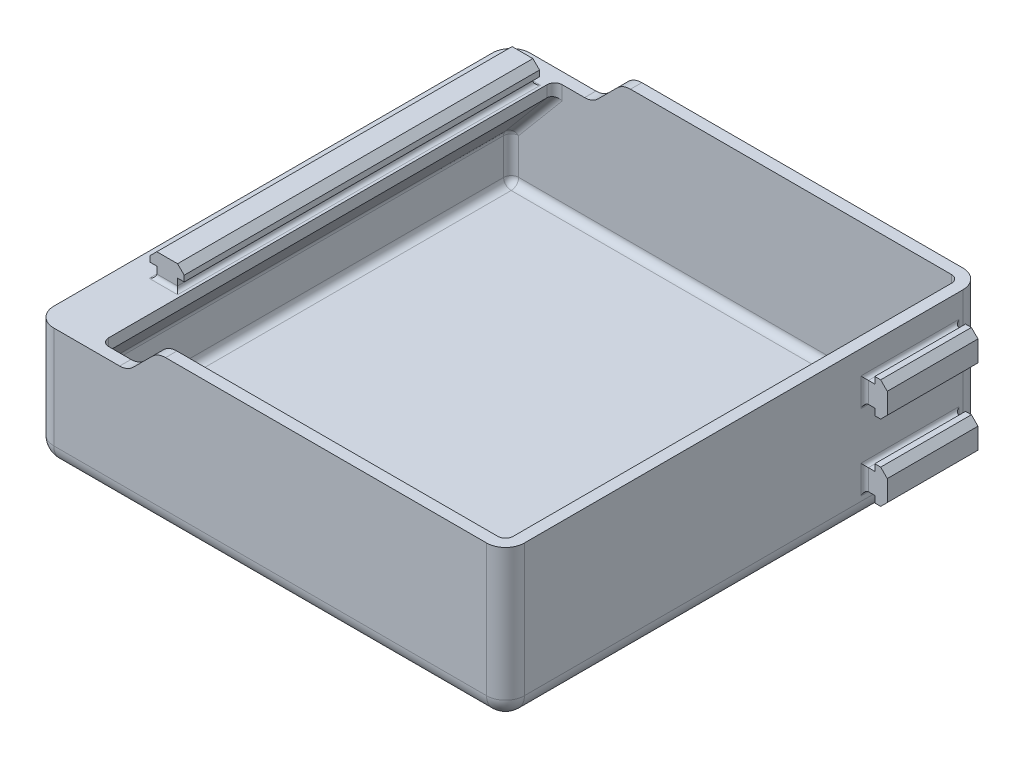
SolidWorks part; units mm, degrees
material "Hot Galvanized Steel"
ref_plane "Front" through (0, 0, 0) normal (0, 0, 1) x (1, 0, 0)
ref_plane "Top" through (0, 0, 0) normal (0, 1, 0) x (1, 0, 0)
ref_plane "Right" through (0, 0, 0) normal (1, 0, 0) x (0, 0, -1)
sketch "Sketch1" plane through (0, 0, 0) normal (0, 1, 0) x (1, 0, 0)
  line L1 (-62.25, -63) -> (62.25, -63)
  line L2 (-62.25, -63) -> (-62.25, 63)
  line L3 (-62.25, 63) -> (62.25, 63)
  line L4 (62.25, -63) -> (62.25, 63)
  line L5 (-62.25, -63) -> (62.25, 63) construction
  line L6 (-62.25, 63) -> (62.25, -63) construction
  point P0 (0, 0)
  dimension "D1" = 124.5
  dimension "D2" = 126
extrude "Boss-Extrude1" add sketch "Sketch1" along normal blind 40
fillet "Fillet1" radius 5 8 edges at (-62.25, 0, 0) (0, 0, -63) (-62.25, 20, -63) (62.25, 20, -63) (62.25, 0, 0) (62.25, 20, 63) (0, 0, 63) (-62.25, 20, 63)
shell "Shell1" thickness 3 removed face at (0, 40, 0)
sketch "Sketch2" plane through (0, 0, 0) normal (0, 0, 1) x (1, 0, 0)
  line L1 (-62.25, 40) -> (-29.75, 40)
  line L2 (-62.25, 40) -> (-62.25, 32)
  line L3 (-62.25, 32) -> (-37.75, 32)
  line L4 (-29.75, 40) -> (-37.75, 32)
  line L5 (62.25, 40) -> (62.25, 5) construction
  point P7 (-30.9427, 40)
  dimension "D1" = 8
  dimension "D2" = 100
  dimension "D3" = 45
extrude "Cut-Extrude1" cut sketch "Sketch2" against normal through all both and the other way through all
sketch "Sketch5" plane through (0, 0, -63) normal (0, 0, -1) x (-1, 0, 0)
  line L0 (-62.25, 32.75) -> (-62.25, 27.25)
  line L2 (-64.95, 25.5) -> (-66.5, 25.5)
  line L3 (-66.5, 25.5) -> (-68.25, 27.25)
  line L4 (-68.25, 27.25) -> (-68.25, 32.75)
  line L5 (-68.25, 32.75) -> (-66.5, 34.5)
  line L6 (-66.5, 34.5) -> (-64.95, 34.5)
  line L7 (-57.25, 40) -> (-62.25, 40) construction
  line L8 (-62.25, 30) -> (-68.25, 30) construction
  line L9 (-62.25, 32.75) -> (-64.95, 32.75)
  line L10 (-64.95, 32.75) -> (-64.95, 34.5)
  line L11 (-64.95, 27.25) -> (-64.95, 25.5)
  line L12 (-62.25, 27.25) -> (-64.95, 27.25)
  line L13 (-62.25, 5) -> (-62.25, 40) construction
  point P1 (-68.2302, 33)
  point P2 (-65, 33)
  point P10 (-65.725, 25.5)
  point P11 (-62.25, 30)
  point P20 (-68.1343, 33)
  dimension "D1" = 6
  dimension "D2" = 9
  dimension "D3" = 2.7
  dimension "D4" = 10
  dimension "D5" = 5.5
extrude "Boss-Extrude3" add sketch "Sketch5" against normal blind 24 from offset 7 offset against normal yes
fillet "Fillet3" radius 1 4 edges at (62.25, 30, -32) (62.25, 30, -56) (62.25, 32.75, -44) (62.25, 27.25, -44)
pattern_linear "LPattern1" count 2 spacing 20 along (0, -1, 0) of "Boss-Extrude3", "Fillet3"
fillet "Fillet4" radius 5 4 edges at (-29.75, 40, 61.5) (-37.75, 32, 61.5) (-29.75, 40, -61.5) (-37.75, 32, -61.5)
sketch "Sketch7" plane through (0, 0, 0) normal (0, 0, 1) x (1, 0, 0)
  line L0 (-47.75, 32) -> (-47.75, 29)
  line L1 (-57.25, 32) -> (-39.8211, 32) construction
  line L2 (-47.75, 29) -> (-59.25, 15.2948)
  line L3 (-59.25, 15.2948) -> (-59.25, 32)
  line L4 (-59.25, 32) -> (-47.75, 32)
  line L5 (-62.25, 32) -> (-62.25, 5) construction
  dimension "D1" = 14.5
  dimension "D2" = 3
  dimension "D3" = 40
extrude "Boss-Extrude5" add sketch "Sketch7" along normal up to next and the other way up to next
sketch "Sketch8" plane through (0, 0, -56) normal (0, 0, -1) x (-1, 0, 0)
  line L0 (55, 32) -> (55, 34.8)
  line L1 (57.25, 32) -> (39.8211, 32) construction
  line L2 (55, 34.8) -> (56.75, 34.8)
  line L3 (56.75, 34.8) -> (56.75, 36.35)
  line L4 (56.75, 36.35) -> (55, 38.1)
  line L6 (52.25, 38.1) -> (52.25, 32) construction
  line L10 (47.75, 36.35) -> (49.5, 38.1)
  line L11 (47.75, 34.8) -> (47.75, 36.35)
  line L12 (49.5, 34.8) -> (47.75, 34.8)
  line L13 (49.5, 32) -> (49.5, 34.8)
  line L15 (49.5, 38.1) -> (55, 38.1)
  line L16 (-68.25, 32.75) -> (-68.25, 27.25) construction
  line L18 (49.5, 32) -> (55, 32)
  line L19 (-64.95, 34.5) -> (-66.5, 34.5) construction
  line L20 (-63.25, 27.25) -> (-63.25, 32.75) construction
  line L22 (62.25, 32) -> (62.25, 5) construction
  line L23 (-66.5, 34.5) -> (-68.25, 32.75) construction
  point P17 (57.4397, 32)
  point P18 (55.4163, 35.4886)
  point P21 (57.4397, 40.1025)
  point P22 (63.0603, 40.1025)
  point P23 (62.5217, 37.6313)
  point P26 (60.25, 41.2979)
  point P27 (0, 0)
  point P28 (60.25, 45.3374)
  point P29 (57.25, 32)
  point P30 (0, 0)
  point P31 (0, 0)
  dimension "D1" = 10
  dimension "D2" = 2.8
extrude "Boss-Extrude6" add sketch "Sketch8" against normal blind 94
fillet "Fillet5" radius 2 5 edges at (-52.5, 23.3392, -60) (-58.6642, 15.9929, -59.4142) (-59.25, 15.2948, 0) (-58.6642, 15.9929, 59.4142) (-52.5, 23.3392, 60)
fillet "Fillet7" radius 2 2 edges at (-47.75, 28.9443, 60) (-47.75, 28.9443, -60)
fillet "Fillet8" radius 1 4 edges at (-52.25, 32, 38) (-55, 32, -9) (-52.25, 32, -56) (-49.5, 32, -9)
